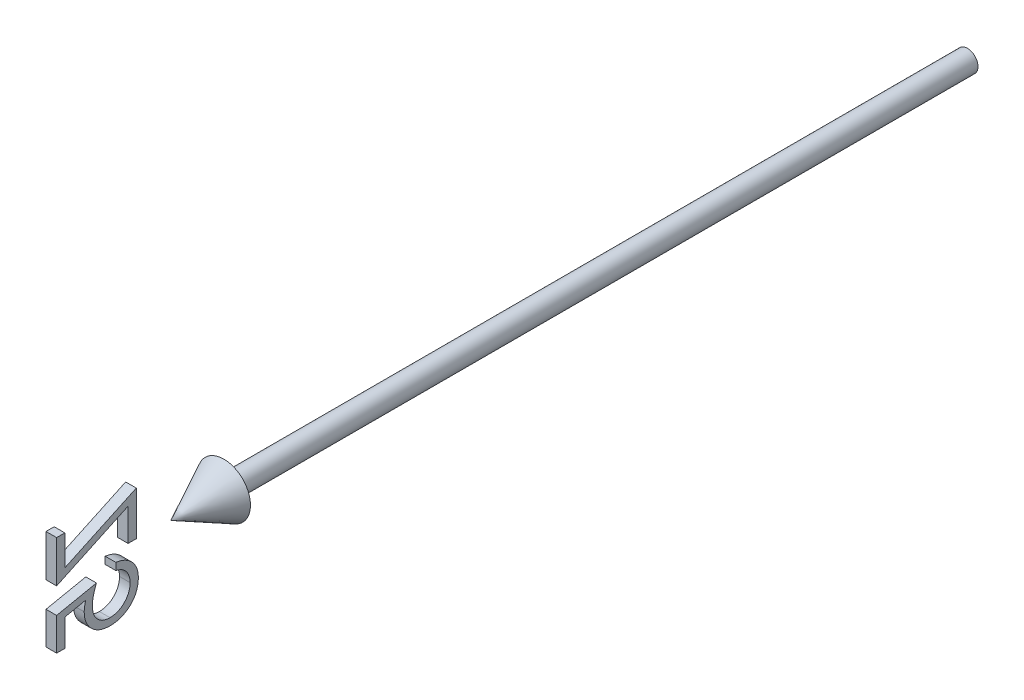
SolidWorks part; units mm, degrees
ref_plane "Front Plane" through (0, 0, 0) normal (0, 0, 1) x (1, 0, 0)
ref_plane "Top Plane" through (0, 0, 0) normal (0, 1, 0) x (1, 0, 0)
ref_plane "Right Plane" through (0, 0, 0) normal (1, 0, 0) x (0, 0, -1)
sketch "Sketch2" plane through (0, 0, 0) normal (0, 1, 0) x (1, 0, 0)
  line L0 (0, 41.95) -> (0, -114.4521) construction
  line L1 (-36.8894, 0) -> (41.4965, 0) construction
  line L2 (0, -150) -> (5, -140)
  line L3 (5, -140) -> (2, -140)
  line L4 (2, -140) -> (2, 0)
  line L5 (2, 0) -> (0, 0)
  line L6 (0, 0) -> (0, -150)
  dimension "D1" = 150
  dimension "D2" = 2
  dimension "D3" = 10
  dimension "D4" = 5
revolve "Revolve1" add sketch "Sketch2" angle 360 about L0
sketch "Sketch3" plane through (0, 0, 0) normal (1, 0, 0) x (0, -1, 0)
  line L0 (0, -101.5706) -> (0, -127.8138) construction
  line L1 (-10.1124, -157.5) -> (14.1256, -157.5) construction
  line L2 (-24.6972, 0) -> (30.3194, 0) construction
  text T0 "Z5\r\n" font "Century Gothic" height 15
  dimension "D1" = 157.5
extrude "Boss-Extrude1" add sketch "Sketch3" against normal blind 1 and the other way blind 1 separate body
equation "\"D1@Sketch2\"=\"frame_arrow_length\""
equation "\"D2@Sketch2\"=\"frame_arrow_odA\"/2"
equation "\"D4@Sketch2\"=\"frame_arrow_head_od\""
equation "\"D3@Sketch2\"=\"frame_arrow_head_length\""
equation "\"frame_arrow_length\"=150"
equation "\"frame_arrow_head_length\"=10"
equation "\"frame_arrow_head_od\"=5"
equation "\"frame_arrow_odA\"=4"
equation "\"D1@Sketch3\"=\"frame_arrow_length\"*1.05"
